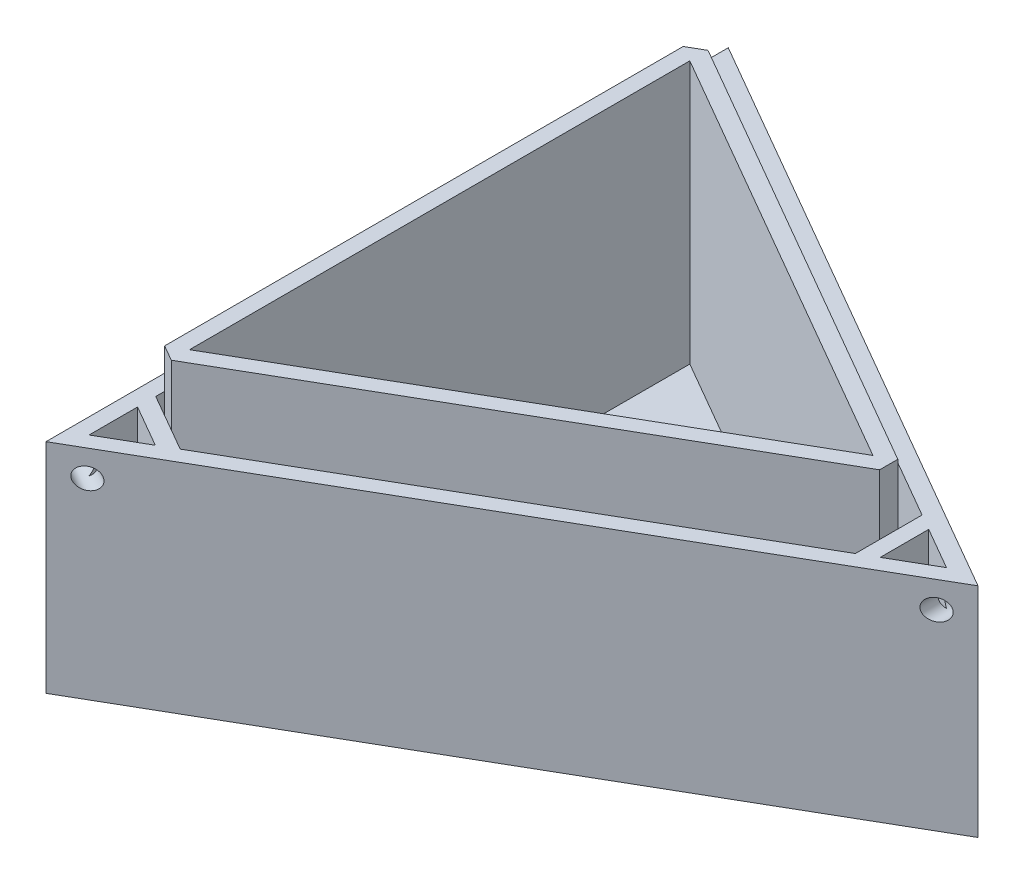
SolidWorks part; units mm, degrees
ref_plane "Front Plane" through (0, 0, 0) normal (0, 0, 1) x (1, 0, 0)
ref_plane "Top Plane" through (0, 0, 0) normal (0, 1, 0) x (1, 0, 0)
ref_plane "Right Plane" through (0, 0, 0) normal (1, 0, 0) x (0, 0, -1)
sketch "Sketch1" plane through (0, 0, 0) normal (0, 1, 0) x (1, 0, 0)
  line L0 (-34.5, 50.5181) -> (-26.5, 55.137)
  line L1 (75, 0) -> (-37.5, 64.9519)
  line L2 (-37.5, 64.9519) -> (-37.5, -64.9519)
  line L3 (-37.5, -64.9519) -> (75, 0)
  line L4 (69, 0) -> (-34.5, 59.7558)
  line L5 (-34.5, 59.7558) -> (-34.5, -59.7558)
  line L6 (-34.5, -59.7558) -> (69, 0)
  line L7 (-13.95, -13.95) -> (13.95, -13.95) construction
  line L8 (-13.95, -13.95) -> (-13.95, 13.95) construction
  line L9 (-13.95, 13.95) -> (13.95, 13.95) construction
  line L10 (13.95, -13.95) -> (13.95, 13.95) construction
  line L11 (-13.95, -13.95) -> (13.95, 13.95) construction
  line L12 (-13.95, 13.95) -> (13.95, -13.95) construction
  line L13 (61, 0) -> (-30.5, 52.8275)
  line L14 (-30.5, 52.8275) -> (-30.5, -52.8275)
  line L15 (-30.5, -52.8275) -> (61, 0)
  line L16 (55, 0) -> (-27.5, 47.6314)
  line L17 (-27.5, 47.6314) -> (-27.5, -47.6314)
  line L18 (-27.5, -47.6314) -> (55, 0)
  line L19 (-34.5, 47.054) -> (-23.5, 53.4049)
  line L20 (61, 4.6188) -> (61, -4.6188)
  line L21 (58, 6.3509) -> (58, -6.3509)
  line L22 (-30.5, 52.8275) -> (-29, 50.2295) construction
  line L23 (-27.5, 0) -> (-30.5, 0) construction
  line L24 (69, 0) -> (70.5, 2.5981) construction
  line L25 (61, 0) -> (58, 0) construction
  line L26 (-37.5, 64.9519) -> (0, 0) construction
  line L27 (-34.5, -50.5181) -> (-26.5, -55.137)
  line L28 (-34.5, -47.054) -> (-23.5, -53.4049)
  line L29 (-30.5, -52.8275) -> (-29, -50.2295) construction
  circle A0 centre (0, 0) radius 37.5 construction
  circle A1 centre (0, 0) radius 34.5 construction
  circle A2 centre (0, 0) radius 9
  circle A3 centre (-13.95, 13.95) radius 1.225
  circle A4 centre (13.95, 13.95) radius 1.225
  circle A5 centre (13.95, -13.95) radius 1.225
  circle A6 centre (-13.95, -13.95) radius 1.225
  circle A7 centre (0, 0) radius 30.5 construction
  circle A8 centre (0, 0) radius 27.5 construction
  point P29 (-30.5, 52.8275)
  point P34 (61, 0)
  point P44 (-30.5, -52.8275)
  dimension "D2" = 3
  dimension "D1" = 75
  dimension "D3" = 18
  dimension "D5" = 2.45
  dimension "D6" = 61
  dimension "D4" = 27.9
extrude "Boss-Extrude1" add sketch "Sketch1" against normal blind 3 contours A2 | A5 | A6 | A3 | A4 | L2 L3 L1 region at (0, 0, 0) region at (-13.95, 0, -13.95) region at (13.95, 0, -13.95) region at (13.95, 0, 13.95) region at (-13.95, 0, 13.95)
extrude "Boss-Extrude2" add sketch "Sketch1<3>" along normal blind 38.5 contours L2 L3 L1 L6 L5 L4 | L5 L19 L14 L0 | L14 L19 L13 | L13 L19 L4 L0 | L4 L21 L13 L20 | L13 L21 L15 | L15 L21 L6 L20 | L28 L5 L27 L14 | L28 L15 L27 L6 | L28 L14 L15 region at (-32.5, 0, -49.9408) region at (-27, 0, -53.1162) region at (-29.5, 0, -51.0955) region at (-32.5, 0, 49.9408) region at (59.5, 0, -3.1754) region at (59, 0, 0) region at (-29.5, 0, 51.0955) region at (59.5, 0, 3.1754) region at (-27, 0, 53.1162) region at (17.8908, 0, 30.9877)
sketch "Sketch1<3>" plane through (0, 0, 0) normal (0, 1, 0) x (1, 0, 0) same geometry as "Sketch1"
extrude "Boss-Extrude4" add sketch "Sketch1<5>" along normal blind 50 contours L14 L28 L15 L21 L13 L19 L18 L17 L16 region at (14.5741, 0, -25.243)
sketch "Sketch1<5>" plane through (0, 0, 0) normal (0, 1, 0) x (1, 0, 0) same geometry as "Sketch1"
ref_plane "Plane1" through (0, 0, 0) normal (0.866, 0, 0.5) x (0.5, 0, -0.866)
sketch "Sketch2" plane through (-5.024, 0, 8.7019) normal (0.866, 0, 0.5) x (0.5, 0, -0.866)
  line L0 (-59.9519, 33.5) -> (-59.9519, 38.5) construction
  line L1 (-64.9519, 38.5) -> (47.5481, 38.5) construction
  line L2 (-59.9519, 33.5) -> (-64.9519, 33.5) construction
  line L3 (-64.9519, -3) -> (-64.9519, 38.5) construction
  circle A0 centre (-59.9519, 33.5) radius 2
  dimension "D1" = 4
  dimension "D2" = 5
extrude "Cut-Extrude1" cut sketch "Sketch2" against normal mid plane 10
ref_plane "Plane2" through (0, 0, 0) normal (-0.866, 0, 0.5) x (0.5, 0, 0.866)
mirror "Mirror1" about plane through (0, 0, 0) normal (-0.866, 0, 0.5) of "Cut-Extrude1"
ref_plane "Plane3" through (0, 0, 0) normal (0, 0, 1) x (1, 0, 0)
mirror "Mirror2" about plane through (0, 0, 0) normal (0, 0, 1) of "Mirror1"
